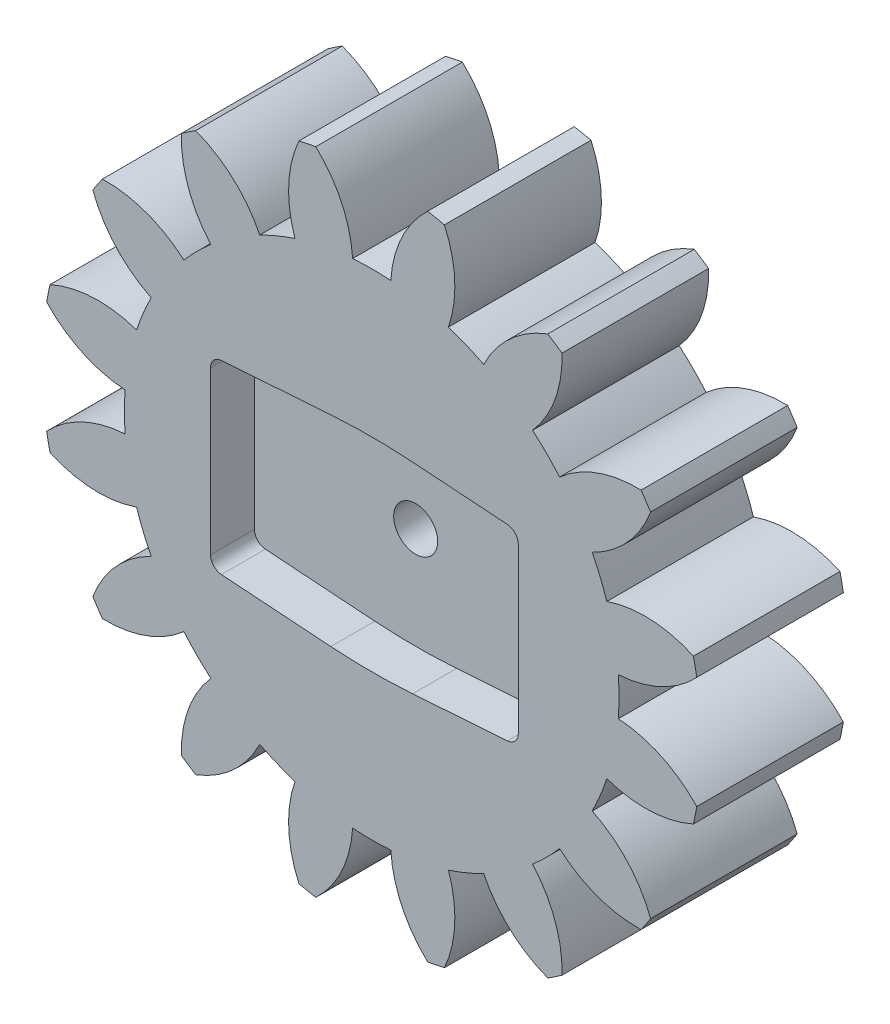
SolidWorks part; units mm, degrees
ref_plane "Alzado" through (0, 0, 0) normal (0, 0, 1) x (1, 0, 0)
ref_plane "Planta" through (0, 0, 0) normal (0, 1, 0) x (1, 0, 0)
ref_plane "Vista lateral" through (0, 0, 0) normal (1, 0, 0) x (0, 0, -1)
sketch "Croquis2" plane through (0, 0, 0) normal (0, 0, 1) x (1, 0, 0)
  circle A0 centre (0, 0) radius 2.5 construction
  circle A1 centre (0, 0) radius 2.5
  circle A2 centre (0, 0) radius 2
  arc A64 (8.4113, 0.6511) -> (11.0871, 1.9076) centre (8.1693, 4.6437) ccw
  arc A65 (11.0871, 1.9076) -> (10.9731, 2.4805) centre (0, 0) ccw
  arc A66 (10.9731, 2.4805) -> (8.0202, 2.6174) centre (9.3246, -1.164) ccw
  arc A67 (8.0202, 2.6174) -> (7.5219, 3.8204) centre (0, 0) ccw
  arc A68 (7.5219, 3.8204) -> (9.5131, 6.0052) centre (5.7704, 7.4165) ccw
  arc A69 (9.5131, 6.0052) -> (9.1886, 6.4909) centre (0, 0) ccw
  arc A70 (9.1886, 6.4909) -> (6.4081, 5.4873) centre (9.0602, 2.493) ccw
  arc A71 (6.4081, 5.4873) -> (5.4873, 6.4081) centre (0, 0) ccw
  arc A72 (5.4873, 6.4081) -> (6.4909, 9.1886) centre (2.493, 9.0602) ccw
  arc A73 (6.4909, 9.1886) -> (6.0052, 9.5131) centre (0, 0) ccw
  arc A74 (6.0052, 9.5131) -> (3.8204, 7.5219) centre (7.4165, 5.7704) ccw
  arc A75 (3.8204, 7.5219) -> (2.6174, 8.0202) centre (0, 0) ccw
  arc A76 (2.6174, 8.0202) -> (2.4805, 10.9731) centre (-1.164, 9.3246) ccw
  arc A77 (2.4805, 10.9731) -> (1.9076, 11.0871) centre (0, 0) ccw
  arc A78 (1.9076, 11.0871) -> (0.6511, 8.4113) centre (4.6437, 8.1693) ccw
  arc A79 (0.6511, 8.4113) -> (-0.6511, 8.4113) centre (0, 0) ccw
  arc A80 (-0.6511, 8.4113) -> (-1.9076, 11.0871) centre (-4.6437, 8.1693) ccw
  arc A81 (-1.9076, 11.0871) -> (-2.4805, 10.9731) centre (0, 0) ccw
  arc A82 (-2.4805, 10.9731) -> (-2.6174, 8.0202) centre (1.164, 9.3246) ccw
  arc A83 (-2.6174, 8.0202) -> (-3.8204, 7.5219) centre (0, 0) ccw
  arc A84 (-3.8204, 7.5219) -> (-6.0052, 9.5131) centre (-7.4165, 5.7704) ccw
  arc A85 (-6.0052, 9.5131) -> (-6.4909, 9.1886) centre (0, 0) ccw
  arc A86 (-6.4909, 9.1886) -> (-5.4873, 6.4081) centre (-2.493, 9.0602) ccw
  arc A87 (-5.4873, 6.4081) -> (-6.4081, 5.4873) centre (0, 0) ccw
  arc A88 (-6.4081, 5.4873) -> (-9.1886, 6.4909) centre (-9.0602, 2.493) ccw
  arc A89 (-9.1886, 6.4909) -> (-9.5131, 6.0052) centre (0, 0) ccw
  arc A90 (-9.5131, 6.0052) -> (-7.5219, 3.8204) centre (-5.7704, 7.4165) ccw
  arc A91 (-7.5219, 3.8204) -> (-8.0202, 2.6174) centre (0, 0) ccw
  arc A92 (-8.0202, 2.6174) -> (-10.9731, 2.4805) centre (-9.3246, -1.164) ccw
  arc A93 (-10.9731, 2.4805) -> (-11.0871, 1.9076) centre (0, 0) ccw
  arc A94 (-11.0871, 1.9076) -> (-8.4113, 0.6511) centre (-8.1693, 4.6437) ccw
  arc A95 (-8.4113, 0.6511) -> (-8.4113, -0.6511) centre (0, 0) ccw
  arc A96 (-8.4113, -0.6511) -> (-11.0871, -1.9076) centre (-8.1693, -4.6437) ccw
  arc A97 (-11.0871, -1.9076) -> (-10.9731, -2.4805) centre (0, 0) ccw
  arc A98 (-10.9731, -2.4805) -> (-8.0202, -2.6174) centre (-9.3246, 1.164) ccw
  arc A99 (-8.0202, -2.6174) -> (-7.5219, -3.8204) centre (0, 0) ccw
  arc A100 (-7.5219, -3.8204) -> (-9.5131, -6.0052) centre (-5.7704, -7.4165) ccw
  arc A101 (-9.5131, -6.0052) -> (-9.1886, -6.4909) centre (0, 0) ccw
  arc A102 (-9.1886, -6.4909) -> (-6.4081, -5.4873) centre (-9.0602, -2.493) ccw
  arc A103 (-6.4081, -5.4873) -> (-5.4873, -6.4081) centre (0, 0) ccw
  arc A104 (-5.4873, -6.4081) -> (-6.4909, -9.1886) centre (-2.493, -9.0602) ccw
  arc A105 (-6.4909, -9.1886) -> (-6.0052, -9.5131) centre (0, 0) ccw
  arc A106 (-6.0052, -9.5131) -> (-3.8204, -7.5219) centre (-7.4165, -5.7704) ccw
  arc A107 (-3.8204, -7.5219) -> (-2.6174, -8.0202) centre (0, 0) ccw
  arc A108 (-2.6174, -8.0202) -> (-2.4805, -10.9731) centre (1.164, -9.3246) ccw
  arc A109 (-2.4805, -10.9731) -> (-1.9076, -11.0871) centre (0, 0) ccw
  arc A110 (-1.9076, -11.0871) -> (-0.6511, -8.4113) centre (-4.6437, -8.1693) ccw
  arc A111 (-0.6511, -8.4113) -> (0.6511, -8.4113) centre (0, 0) ccw
  arc A112 (0.6511, -8.4113) -> (1.9076, -11.0871) centre (4.6437, -8.1693) ccw
  arc A113 (1.9076, -11.0871) -> (2.4805, -10.9731) centre (0, 0) ccw
  arc A114 (2.4805, -10.9731) -> (2.6174, -8.0202) centre (-1.164, -9.3246) ccw
  arc A115 (2.6174, -8.0202) -> (3.8204, -7.5219) centre (0, 0) ccw
  arc A116 (3.8204, -7.5219) -> (6.0052, -9.5131) centre (7.4165, -5.7704) ccw
  arc A117 (6.0052, -9.5131) -> (6.4909, -9.1886) centre (0, 0) ccw
  arc A118 (6.4909, -9.1886) -> (5.4873, -6.4081) centre (2.493, -9.0602) ccw
  arc A119 (5.4873, -6.4081) -> (6.4081, -5.4873) centre (0, 0) ccw
  arc A120 (6.4081, -5.4873) -> (9.1886, -6.4909) centre (9.0602, -2.493) ccw
  arc A121 (9.1886, -6.4909) -> (9.5131, -6.0052) centre (0, 0) ccw
  arc A122 (9.5131, -6.0052) -> (7.5219, -3.8204) centre (5.7704, -7.4165) ccw
  arc A123 (7.5219, -3.8204) -> (8.0202, -2.6174) centre (0, 0) ccw
  arc A124 (8.0202, -2.6174) -> (10.9731, -2.4805) centre (9.3246, 1.164) ccw
  arc A125 (10.9731, -2.4805) -> (11.0871, -1.9076) centre (0, 0) ccw
  arc A126 (11.0871, -1.9076) -> (8.4113, -0.6511) centre (8.1693, -4.6437) ccw
  arc A127 (8.4113, -0.6511) -> (8.4113, 0.6511) centre (0, 0) ccw
  arc A128 (8.4113, 0.6511) -> (11.0871, 1.9076) centre (8.1693, 4.6437) ccw
  arc A129 (11.0871, 1.9076) -> (10.9731, 2.4805) centre (0, 0) ccw
  arc A130 (10.9731, 2.4805) -> (8.0202, 2.6174) centre (9.3246, -1.164) ccw
  arc A131 (8.0202, 2.6174) -> (7.5219, 3.8204) centre (0, 0) ccw
  arc A132 (7.5219, 3.8204) -> (9.5131, 6.0052) centre (5.7704, 7.4165) ccw
  arc A133 (9.5131, 6.0052) -> (9.1886, 6.4909) centre (0, 0) ccw
  arc A134 (9.1886, 6.4909) -> (6.4081, 5.4873) centre (9.0602, 2.493) ccw
  arc A135 (6.4081, 5.4873) -> (5.4873, 6.4081) centre (0, 0) ccw
  arc A136 (5.4873, 6.4081) -> (6.4909, 9.1886) centre (2.493, 9.0602) ccw
  arc A137 (6.4909, 9.1886) -> (6.0052, 9.5131) centre (0, 0) ccw
  arc A138 (6.0052, 9.5131) -> (3.8204, 7.5219) centre (7.4165, 5.7704) ccw
  arc A139 (3.8204, 7.5219) -> (2.6174, 8.0202) centre (0, 0) ccw
  arc A140 (2.6174, 8.0202) -> (2.4805, 10.9731) centre (-1.164, 9.3246) ccw
  arc A141 (2.4805, 10.9731) -> (1.9076, 11.0871) centre (0, 0) ccw
  arc A142 (1.9076, 11.0871) -> (0.6511, 8.4113) centre (4.6437, 8.1693) ccw
  arc A143 (0.6511, 8.4113) -> (-0.6511, 8.4113) centre (0, 0) ccw
  arc A144 (-0.6511, 8.4113) -> (-1.9076, 11.0871) centre (-4.6437, 8.1693) ccw
  arc A145 (-1.9076, 11.0871) -> (-2.4805, 10.9731) centre (0, 0) ccw
  arc A146 (-2.4805, 10.9731) -> (-2.6174, 8.0202) centre (1.164, 9.3246) ccw
  arc A147 (-2.6174, 8.0202) -> (-3.8204, 7.5219) centre (0, 0) ccw
  arc A148 (-3.8204, 7.5219) -> (-6.0052, 9.5131) centre (-7.4165, 5.7704) ccw
  arc A149 (-6.0052, 9.5131) -> (-6.4909, 9.1886) centre (0, 0) ccw
  arc A150 (-6.4909, 9.1886) -> (-5.4873, 6.4081) centre (-2.493, 9.0602) ccw
  arc A151 (-5.4873, 6.4081) -> (-6.4081, 5.4873) centre (0, 0) ccw
  arc A152 (-6.4081, 5.4873) -> (-9.1886, 6.4909) centre (-9.0602, 2.493) ccw
  arc A153 (-9.1886, 6.4909) -> (-9.5131, 6.0052) centre (0, 0) ccw
  arc A154 (-9.5131, 6.0052) -> (-7.5219, 3.8204) centre (-5.7704, 7.4165) ccw
  arc A155 (-7.5219, 3.8204) -> (-8.0202, 2.6174) centre (0, 0) ccw
  arc A156 (-8.0202, 2.6174) -> (-10.9731, 2.4805) centre (-9.3246, -1.164) ccw
  arc A157 (-10.9731, 2.4805) -> (-11.0871, 1.9076) centre (0, 0) ccw
  arc A158 (-11.0871, 1.9076) -> (-8.4113, 0.6511) centre (-8.1693, 4.6437) ccw
  arc A159 (-8.4113, 0.6511) -> (-8.4113, -0.6511) centre (0, 0) ccw
  arc A160 (-8.4113, -0.6511) -> (-11.0871, -1.9076) centre (-8.1693, -4.6437) ccw
  arc A161 (-11.0871, -1.9076) -> (-10.9731, -2.4805) centre (0, 0) ccw
  arc A162 (-10.9731, -2.4805) -> (-8.0202, -2.6174) centre (-9.3246, 1.164) ccw
  arc A163 (-8.0202, -2.6174) -> (-7.5219, -3.8204) centre (0, 0) ccw
  arc A164 (-7.5219, -3.8204) -> (-9.5131, -6.0052) centre (-5.7704, -7.4165) ccw
  arc A165 (-9.5131, -6.0052) -> (-9.1886, -6.4909) centre (0, 0) ccw
  arc A166 (-9.1886, -6.4909) -> (-6.4081, -5.4873) centre (-9.0602, -2.493) ccw
  arc A167 (-6.4081, -5.4873) -> (-5.4873, -6.4081) centre (0, 0) ccw
  arc A168 (-5.4873, -6.4081) -> (-6.4909, -9.1886) centre (-2.493, -9.0602) ccw
  arc A169 (-6.4909, -9.1886) -> (-6.0052, -9.5131) centre (0, 0) ccw
  arc A170 (-6.0052, -9.5131) -> (-3.8204, -7.5219) centre (-7.4165, -5.7704) ccw
  arc A171 (-3.8204, -7.5219) -> (-2.6174, -8.0202) centre (0, 0) ccw
  arc A172 (-2.6174, -8.0202) -> (-2.4805, -10.9731) centre (1.164, -9.3246) ccw
  arc A173 (-2.4805, -10.9731) -> (-1.9076, -11.0871) centre (0, 0) ccw
  arc A174 (-1.9076, -11.0871) -> (-0.6511, -8.4113) centre (-4.6437, -8.1693) ccw
  arc A175 (-0.6511, -8.4113) -> (0.6511, -8.4113) centre (0, 0) ccw
  arc A176 (0.6511, -8.4113) -> (1.9076, -11.0871) centre (4.6437, -8.1693) ccw
  arc A177 (1.9076, -11.0871) -> (2.4805, -10.9731) centre (0, 0) ccw
  arc A178 (2.4805, -10.9731) -> (2.6174, -8.0202) centre (-1.164, -9.3246) ccw
  arc A179 (2.6174, -8.0202) -> (3.8204, -7.5219) centre (0, 0) ccw
  arc A180 (3.8204, -7.5219) -> (6.0052, -9.5131) centre (7.4165, -5.7704) ccw
  arc A181 (6.0052, -9.5131) -> (6.4909, -9.1886) centre (0, 0) ccw
  arc A182 (6.4909, -9.1886) -> (5.4873, -6.4081) centre (2.493, -9.0602) ccw
  arc A183 (5.4873, -6.4081) -> (6.4081, -5.4873) centre (0, 0) ccw
  arc A184 (6.4081, -5.4873) -> (9.1886, -6.4909) centre (9.0602, -2.493) ccw
  arc A185 (9.1886, -6.4909) -> (9.5131, -6.0052) centre (0, 0) ccw
  arc A186 (9.5131, -6.0052) -> (7.5219, -3.8204) centre (5.7704, -7.4165) ccw
  arc A187 (7.5219, -3.8204) -> (8.0202, -2.6174) centre (0, 0) ccw
  arc A188 (8.0202, -2.6174) -> (10.9731, -2.4805) centre (9.3246, 1.164) ccw
  arc A189 (10.9731, -2.4805) -> (11.0871, -1.9076) centre (0, 0) ccw
  arc A190 (11.0871, -1.9076) -> (8.4113, -0.6511) centre (8.1693, -4.6437) ccw
  arc A191 (8.4113, -0.6511) -> (8.4113, 0.6511) centre (0, 0) ccw
  dimension "D2" = 0.5
  dimension "D3" = 9.3969
  dimension "D1" = 0
extrude "Saliente-Extruir1" add sketch "Croquis2" along normal blind 5 contours A190 A191 A128 A129 A130 A131 A132 A133 A134 A135 A136 A137 A138 A139 A140 A141 A142 A143 A144 A145 A146 A147 A148 A149 A150 A151 A152 A153 A154 A155 A156 A157 A158 A159 A160 A161 A162 A163 A164 A165 A166 A167 A168 A169 A170 A171 A172 A173 A174 A175 A176 | A1 region at (8.1229, 0, 0)
sketch "Croquis3" plane through (0, 0, 5) normal (0, 0, 1) x (1, 0, 0)
  line L0 (0, 8.4365) -> (0, -8.4365) construction
  line L1 (0, -8.4365) -> (-8.4365, 0) construction
  line L2 (-8.4365, 0) -> (8.4365, 0) construction
  line L3 (8.4365, 0) -> (0, 8.4365) construction
  line L4 (0, 8.4365) -> (-8.4365, 0) construction
  line L5 (0, -8.4365) -> (8.4365, 0) construction
  line L6 (-5.9655, 5.9655) -> (-5.9655, -5.9655) construction
  line L7 (-5.9655, -5.9655) -> (5.9655, -5.9655) construction
  line L8 (5.9655, -5.9655) -> (5.9655, 5.9655) construction
  line L9 (5.9655, 5.9655) -> (-5.9655, 5.9655) construction
  line L10 (-5.9655, 5.9655) -> (5.9655, -5.9655) construction
  line L11 (5.9655, 5.9655) -> (-5.9655, -5.9655) construction
  arc A0 (3.8204, 7.5219) -> (2.6174, 8.0202) centre (0, 0) ccw construction
  arc A1 (3.8204, 7.5219) -> (2.6174, 8.0202) centre (0, 0) ccw construction
  circle A2 centre (0, 0) radius 2.25
  arc A3 (0.6511, 8.4113) -> (-0.6511, 8.4113) centre (0, 0) ccw construction
  arc A4 (-0.6511, -8.4113) -> (0.6511, -8.4113) centre (0, 0) ccw construction
  arc A5 (-8.4113, 0.6511) -> (-8.4113, -0.6511) centre (0, 0) ccw construction
  arc A6 (8.4113, -0.6511) -> (8.4113, 0.6511) centre (0, 0) ccw construction
  arc A7 (-5.4873, 6.4081) -> (-6.4081, 5.4873) centre (0, 0) ccw construction
  arc A8 (-6.4081, -5.4873) -> (-5.4873, -6.4081) centre (0, 0) ccw construction
  arc A9 (5.4873, -6.4081) -> (6.4081, -5.4873) centre (0, 0) ccw construction
  arc A10 (6.4081, 5.4873) -> (5.4873, 6.4081) centre (0, 0) ccw construction
  circle A11 centre (0, 4.75) radius 0.75
  circle A13 centre (4.75, 0) radius 0.75
  circle A15 centre (0, -4.75) radius 0.75
  circle A17 centre (-4.75, 0) radius 0.75
  circle A27 centre (0, 0) radius 7.2365
  circle A28 centre (0, 0) radius 2.75
  arc A29 (-8.0202, -2.6174) -> (-7.5219, -3.8204) centre (0, 0) ccw construction
  point P40 (0, 2.25)
  dimension "D1" = 4.5
  dimension "D2" = 1.5
  dimension "D7" = 0.5
  dimension "D8" = 1.2
  dimension "D5" = 2.5
  dimension "D6" = 4
sketch "Croquis4" plane through (0, 0, 5) normal (0, 0, 1) x (1, 0, 0)
  line L0 (-14.6744, -2.4939) -> (-1.3951, -3.4225)
  line L1 (1.3951, -3.4225) -> (14.6744, -2.4939)
  line L2 (14.6744, 2.4939) -> (1.3951, 3.4225)
  line L3 (-1.3951, 3.4225) -> (-14.6744, 2.4939)
  line L4 (-14.5, 0) -> (14.5, 0) construction
  line L5 (-14.6744, 2.4939) -> (14.6744, 2.4939) construction
  line L6 (-5.5, 3.1354) -> (-5.5, -3.1354)
  line L7 (5, 3.1704) -> (5, -3.1704)
  circle A0 centre (0, 0) radius 1.5
  circle A1 centre (0, 0) radius 0.75
  arc A2 (-1.3951, -3.4225) -> (1.3951, -3.4225) centre (0, 16.5288) ccw
  arc A3 (14.6744, -2.4939) -> (14.6744, 2.4939) centre (14.5, 0) ccw
  arc A4 (1.3951, 3.4225) -> (-1.3951, 3.4225) centre (0, -16.5288) ccw
  arc A5 (-14.6744, 2.4939) -> (-14.6744, -2.4939) centre (-14.5, 0) ccw
  point P17 (0, 3.4712)
  dimension "D1" = 2.5
  dimension "D2" = 20
  dimension "D3" = 1.5
  dimension "D4" = 3
  dimension "D5" = 4
  dimension "D6" = 29
  dimension "D7" = 5.5
  dimension "D8" = 5
extrude "Cortar-Extruir1" cut sketch "Croquis4" against normal up to next contours A1
extrude "Cortar-Extruir2" cut sketch "Croquis4<3>" along normal blind 1.5 from surface contours A0 A1 region at (-1.4576, 0, 5) starting at face at (0.75, 0, 0)
sketch "Croquis4<3>" plane through (0, 0, 5) normal (0, 0, 1) x (1, 0, 0) same geometry as "Croquis4"
extrude "Cortar-Extruir3" cut sketch "Croquis4<4>" against normal blind 1.5 contours A0 A1 | L2 A4 L3 L6 L0 A2 L1 L7 A0 region at (-5.3741, 0, 5) region at (-1.4576, 0, 5)
sketch "Croquis4<4>" plane through (0, 0, 5) normal (0, 0, 1) x (1, 0, 0) same geometry as "Croquis4"
fillet "Redondeo2" radius 0.4 4 edges at (-5.5, -3.1354, 4.25) (-5.5, 3.1354, 4.25) (5, 3.1704, 4.25) (5, -3.1704, 4.25)
